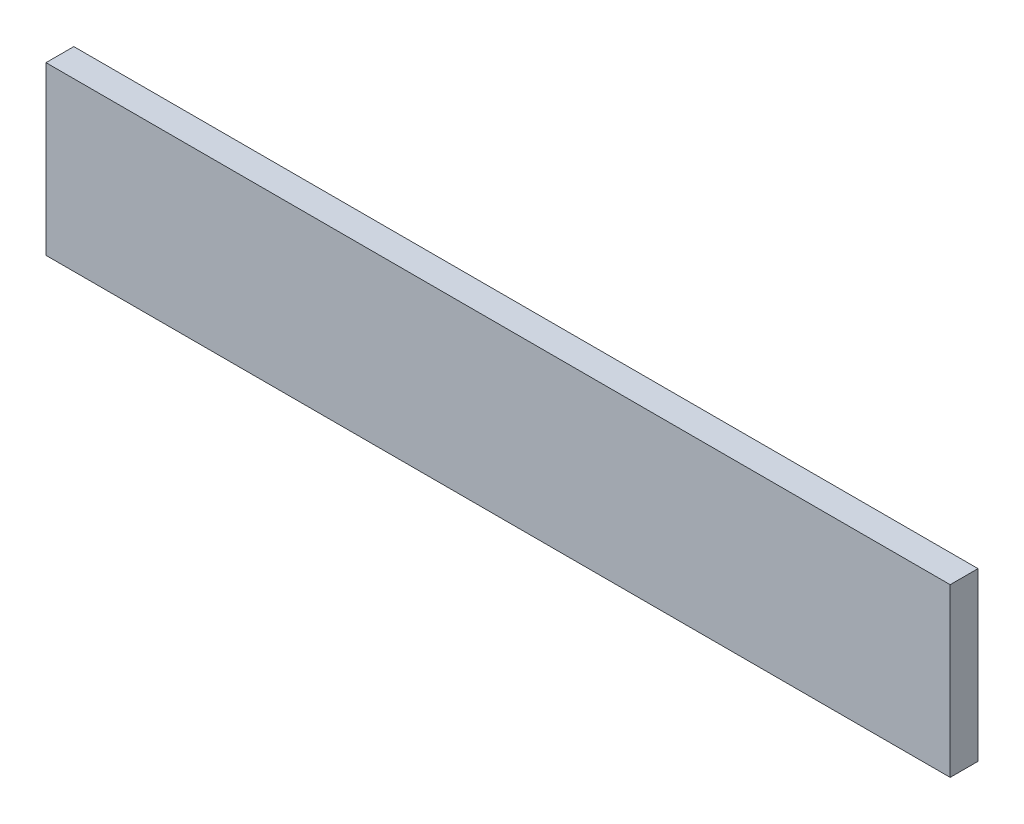
SolidWorks part; units mm, degrees
ref_plane "Front Plane" through (0, 0, 0) normal (0, 0, 1) x (1, 0, 0)
ref_plane "Top Plane" through (0, 0, 0) normal (0, 1, 0) x (1, 0, 0)
ref_plane "Right Plane" through (0, 0, 0) normal (1, 0, 0) x (0, 0, -1)
sketch "Sketch1" plane through (0, 0, 0) normal (0, 0, 1) x (1, 0, 0)
  line L1 (0, 0) -> (650, 0)
  line L2 (0, 0) -> (0, 120)
  line L3 (0, 120) -> (650, 120)
  line L4 (650, 0) -> (650, 120)
  dimension "D1" = 650
  dimension "D2" = 120
extrude "Boss-Extrude1" add sketch "Sketch1" along normal blind 20
